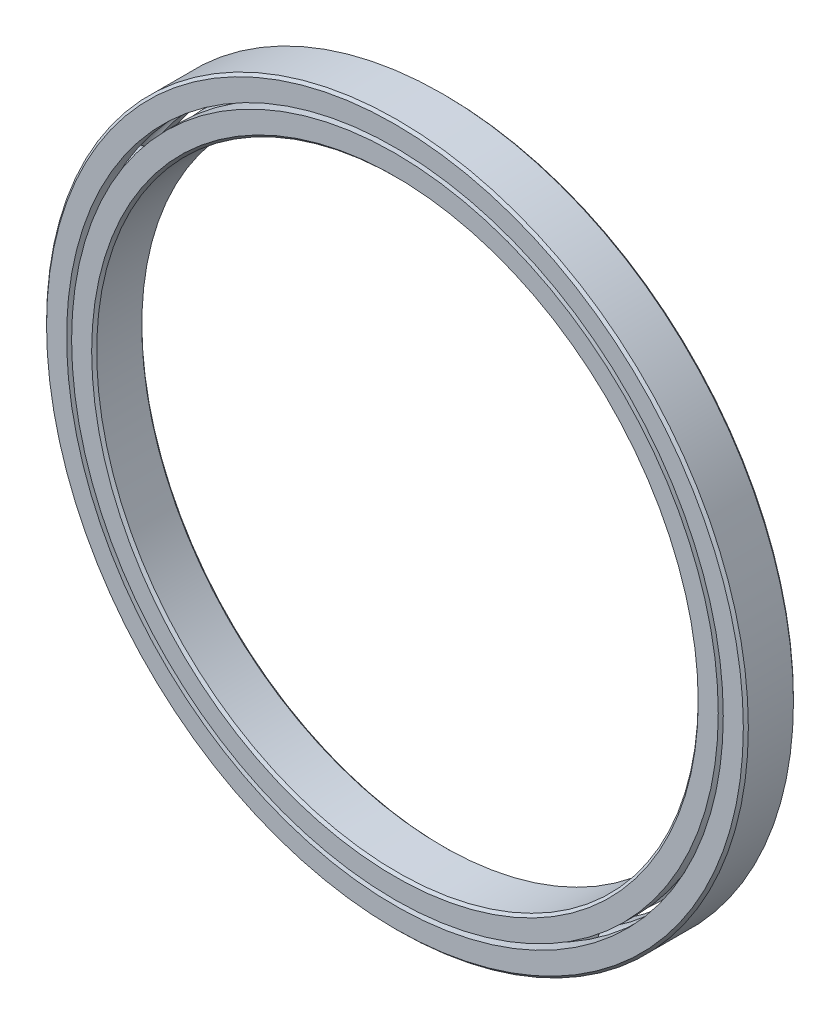
SolidWorks part; units mm, degrees
ref_plane "Front Plane" through (0, 0, 0) normal (0, 0, 1) x (1, 0, 0)
ref_plane "Top Plane" through (0, 0, 0) normal (0, 1, 0) x (1, 0, 0)
ref_plane "Right Plane" through (0, 0, 0) normal (1, 0, 0) x (0, 0, -1)
sketch "Sketch1" plane through (0, 0, 0) normal (1, 0, 0) x (0, 0, -1)
  line L0 (-3.175, 0) -> (3.175, 0) construction
  line L1 (0, 44.45) -> (0, -44.45) construction
  line L2 (2.8575, 44.45) -> (-2.8575, 44.45)
  line L3 (-2.8575, 44.45) -> (-3.175, 44.1325)
  line L4 (-3.175, 44.1325) -> (-3.175, 41.5925)
  line L5 (-3.175, 41.5925) -> (-1.4111, 41.5925)
  line L6 (3.175, 41.5925) -> (1.4111, 41.5925)
  line L7 (3.175, 44.1325) -> (3.175, 41.5925)
  line L8 (2.8575, 44.45) -> (3.175, 44.1325)
  line L9 (0, 44.45) -> (0, 41.275) construction
  line L10 (0, 41.275) -> (0, 38.1) construction
  arc A0 (-1.4111, 41.5925) -> (1.4111, 41.5925) centre (0, 41.275) cw
  point P14 (0, 38.1)
  dimension "Width" = 6.35
  dimension "OD" = 88.9
  dimension "D1" = 45
  dimension "D2" = 0.3175
  dimension "Shaft Dia" = 76.2
  dimension "D3" = 2.8222
  dimension "D4" = 0.3175
revolve "Revolve1" add sketch "Sketch1" angle 360 about L0
sketch "Sketch3" plane through (0, 0, 0) normal (1, 0, 0) x (0, 0, -1)
  line L0 (-3.175, 40.9575) -> (-1.4111, 40.9575)
  line L1 (0, 44.45) -> (0, -44.45) construction
  line L2 (-3.175, 44.1325) -> (-3.175, 41.5925) construction
  line L3 (-3.175, 40.9575) -> (-3.175, 38.4175)
  line L4 (-2.8575, 44.45) -> (-3.175, 44.1325) construction
  line L5 (-3.175, 38.4175) -> (-2.8575, 38.1)
  line L6 (-2.8575, 38.1) -> (2.8575, 38.1)
  line L7 (2.8575, 44.45) -> (2.8575, -44.45) construction
  line L8 (2.8575, 38.1) -> (3.175, 38.4175)
  line L9 (3.175, -44.1325) -> (3.175, 44.1325) construction
  line L10 (3.175, 38.4175) -> (3.175, 40.9575)
  line L11 (3.175, 40.9575) -> (1.4111, 40.9575)
  line L13 (2.8575, 44.45) -> (3.175, 44.1325) construction
  arc A0 (1.4111, 41.5925) -> (-1.4111, 41.5925) centre (0, 41.275) ccw construction
  arc A1 (1.4111, 40.9575) -> (-1.4111, 40.9575) centre (0, 41.275) cw
revolve "Revolve3" add sketch "Sketch3" angle 360 about L0
sketch "Sketch4" plane through (0, 0, 0) normal (1, 0, 0) x (0, 0, -1)
  line L0 (-1.4464, 41.275) -> (1.4464, 41.275)
  arc A2 (-1.4464, 41.275) -> (1.4464, 41.275) centre (0, 41.275) cw
  arc A3 (1.4111, 41.5925) -> (-1.4111, 41.5925) centre (0, 41.275) ccw construction
revolve "Revolve4" add sketch "Sketch4" angle 360 about L0
ref_axis "Axis1" through (0, 0, -3.175) along (0, 0, 1)
pattern_circular "CirPattern1" count 12 over 360 about axis through (0, 0, -3.175) along (0, 0, 1) of bodies 104
equation "\"D2@Sketch1\" = \"Width@Sketch1\"*.05"
equation "\"D3@Sketch1\" = \"Width@Sketch1\"/2.25"
equation "\"D4@Sketch1\" = (((\"OD@Sketch1\"-\"Width@Sketch1\")/2)/3.25)*.025"
equation "\"D2@CirPattern1\" = 360/\"Balls@CirPattern1\""
